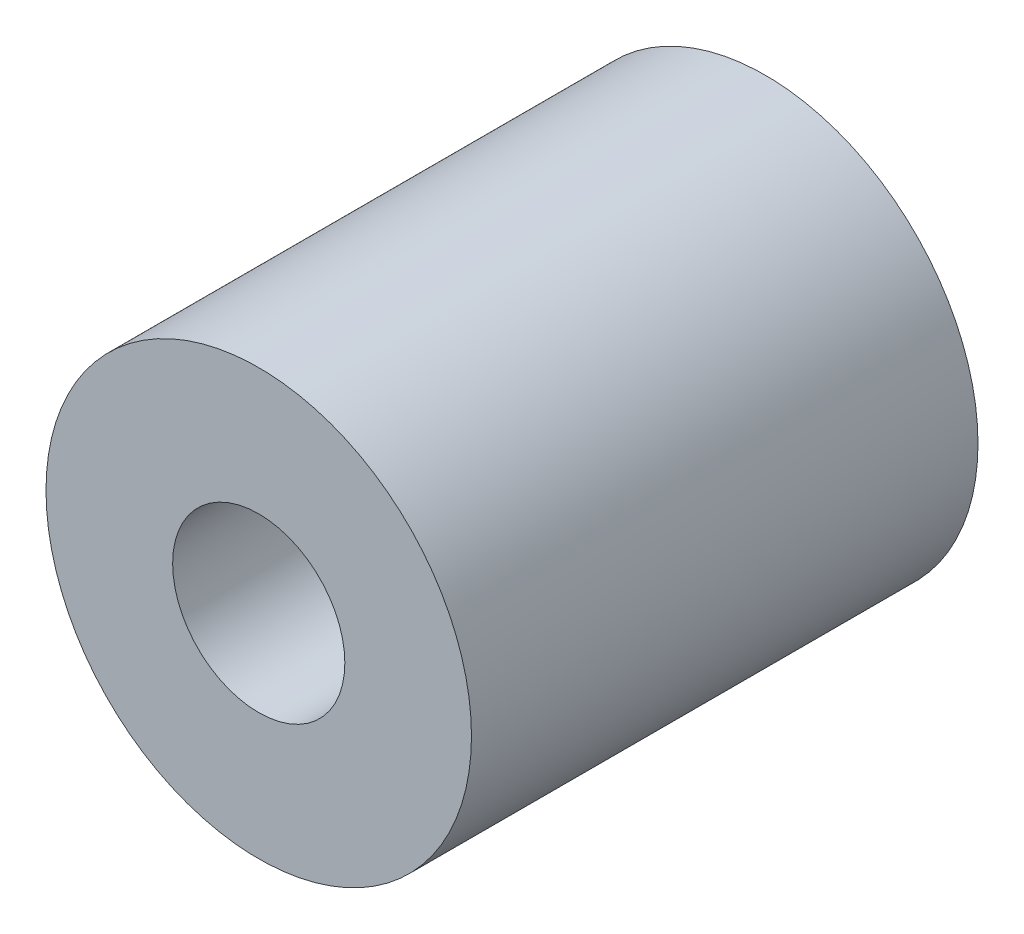
SolidWorks part; units mm, degrees
ref_plane "Front Plane" through (0, 0, 0) normal (0, 0, 1) x (1, 0, 0)
ref_plane "Top Plane" through (0, 0, 0) normal (0, 1, 0) x (1, 0, 0)
ref_plane "Right Plane" through (0, 0, 0) normal (1, 0, 0) x (0, 0, -1)
sketch "Sketch1" plane through (0, 0, 0) normal (0, 1, 0) x (1, 0, 0)
  line L0 (2.125, -3.75) -> (5.25, -3.75)
  line L1 (5.25, -3.75) -> (5.25, 0)
  line L2 (5.25, 0) -> (2.125, 0)
  line L3 (2.125, 0) -> (2.125, -3.75)
  line L4 (0, 0) -> (0, -3.75) construction
  dimension "D1" = 2.125
  dimension "D2" = 5.25
  dimension "D3" = 3.75
revolve "Revolve1" add sketch "Sketch1" angle 360 about L4 reverse direction yes
sketch "Sketch2" plane through (0, 0, 3.75) normal (0, 0, 1) x (1, 0, 0)
  circle A0 centre (0, 0) radius 2.125
  circle A1 centre (0, 0) radius 5.25
  dimension "D1" = 4.25
  dimension "D2" = 10.5
extrude "Boss-Extrude1" add sketch "Sketch2" along normal blind 9.25
sketch "Sketch3" plane through (0, 0, 0) normal (0, 0, -1) x (-1, 0, 0)
  circle A0 centre (0, 0) radius 3
  circle A1 centre (0, 0) radius 5.25
  circle A2 centre (0, 0) radius 5.25
  dimension "D2" = 6
  dimension "D1" = 0
extrude "Cut-Extrude1" cut sketch "Sketch3" against normal blind 0.5
